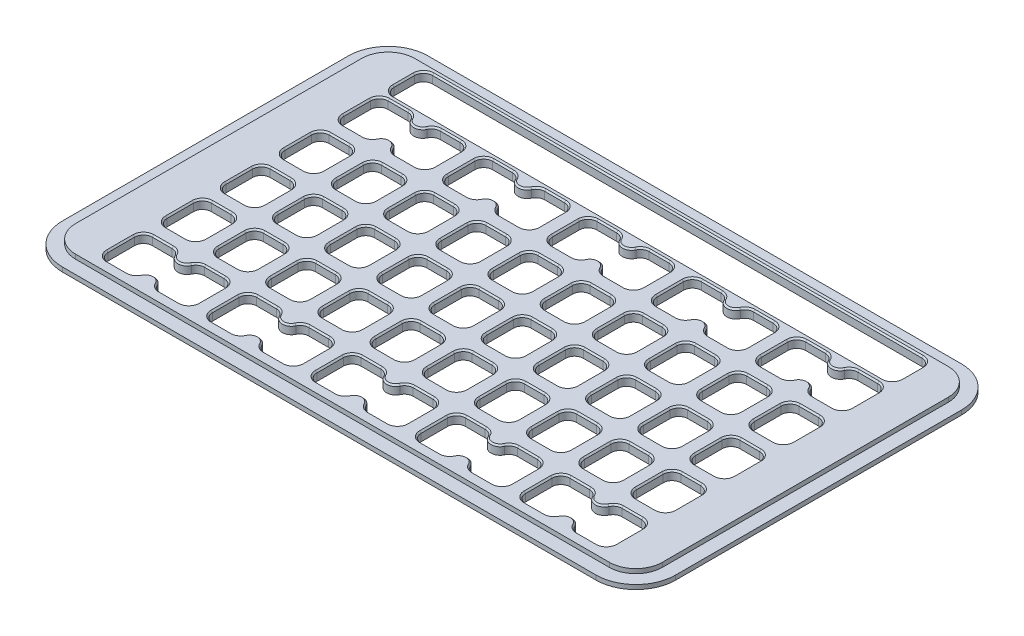
SolidWorks part; units mm, degrees
ref_plane "Front Plane" through (0, 0, 0) normal (0, 0, 1) x (1, 0, 0)
ref_plane "Top Plane" through (0, 0, 0) normal (0, 1, 0) x (1, 0, 0)
ref_plane "Right Plane" through (0, 0, 0) normal (1, 0, 0) x (0, 0, -1)
sketch "Sketch1" plane through (0, 0, 0) normal (0, 1, 0) x (1, 0, 0)
  line L1 (-104, -62) -> (104, -62)
  line L2 (-104, -62) -> (-104, 62)
  line L3 (-104, 62) -> (104, 62)
  line L4 (104, -62) -> (104, 62)
  line L5 (-104, -62) -> (104, 62) construction
  line L6 (-104, 62) -> (104, -62) construction
  point P0 (0, 0)
  dimension "D1" = 208
  dimension "D2" = 124
extrude "Outer Profile" add sketch "Sketch1" along normal blind 1.5
sketch "Sketch2" plane through (0, 1.5, 0) normal (0, 1, 0) x (1, 0, 0)
  line L1 (-99.5, -57.5) -> (99.5, -57.5)
  line L2 (-99.5, -57.5) -> (-99.5, 57.5)
  line L3 (-99.5, 57.5) -> (99.5, 57.5)
  line L4 (99.5, -57.5) -> (99.5, 57.5)
  line L5 (-99.5, -57.5) -> (99.5, 57.5) construction
  line L6 (-99.5, 57.5) -> (99.5, -57.5) construction
  point P0 (0, 0)
  dimension "D1" = 199
  dimension "D2" = 115
extrude "Inner Profile" add sketch "Sketch2" along normal blind 1.5
fillet "Fillet1" radius 9 4 edges at (99.5, 2.25, 57.5) (99.5, 2.25, -57.5) (-99.5, 2.25, -57.5) (-99.5, 2.25, 57.5)
fillet "Fillet2" radius 13.5 4 edges at (-104, 0.75, -62) (104, 0.75, -62) (104, 0.75, 62) (-104, 0.75, 62)
sketch "Sketch3" plane through (0, 3, 0) normal (0, 1, 0) x (1, 0, 0)
  line L1 (-86, -54) -> (86, -54) construction
  line L2 (-86, -54) -> (-86, 54) construction
  line L3 (-86, 54) -> (86, 54) construction
  line L4 (86, -54) -> (86, 54) construction
  line L5 (-86, -54) -> (86, 54) construction
  line L6 (-86, 54) -> (86, -54) construction
  point P0 (0, 0)
  dimension "D1" = 172
  dimension "D2" = 108
sketch "Sketch4" plane through (0, 3, 0) normal (0, 1, 0) x (1, 0, 0)
  line L0 (-86, -54) -> (-86, 54) construction
  line L1 (-86, 43) -> (86, 43)
  line L2 (-86, 43) -> (-86, 56)
  line L3 (-86, 56) -> (86, 56)
  line L4 (86, 43) -> (86, 56)
  line L10 (-86, 54) -> (86, 54) construction
  dimension "D1" = 2
  dimension "D2" = 11
  dimension "D3" = 172
extrude "Message Bar" cut sketch "Sketch4" against normal through all
sketch "Sketch5" plane through (0, 3, 0) normal (0, 1, 0) x (1, 0, 0)
  line L0 (-86, -54) -> (86, -54) construction
  line L1 (-12.2, -54) -> (-5.5, -54)
  line L2 (-15.2, -51) -> (-15.2, -42)
  line L3 (-12.2, -39) -> (-5.5, -39)
  line L4 (-2.5, -51) -> (-2.5, -42)
  line L5 (-8.85, -39) -> (-8.85, -54) construction
  line L6 (0, 0) -> (0, -37.3494) construction
  line L7 (-86, -54) -> (86, 54) construction
  arc A0 (-5.5, -54) -> (-2.5, -51) centre (-5.5, -51) ccw
  arc A1 (-12.2, -54) -> (-15.2, -51) centre (-12.2, -51) cw
  arc A2 (-5.5, -39) -> (-2.5, -42) centre (-5.5, -42) cw
  arc A3 (-15.2, -42) -> (-12.2, -39) centre (-12.2, -42) cw
  point P15 (-2.5, -54)
  point P18 (-15.2, -54)
  point P23 (-15.2, -39)
  dimension "D4" = 3
  dimension "D1" = 12.7
  dimension "D2" = 15
  dimension "D3" = 8.85
extrude "Cutout" cut sketch "Sketch5" against normal through all
pattern_linear "Cutouts" count 5 spacing 17.7 along (-1, 0, 0) count 5 spacing 20 along (0, 0, -1) of "Cutout"
mirror "Mirror Cutouts" about plane through (0, 0, 0) normal (1, 0, 0) of "Cutouts", "Cutout"
fillet "Corner Rad" radius 3 4 edges at (86, 1.5, -43) (86, 1.5, -56) (-86, 1.5, -43) (-86, 1.5, -56)
sketch "Sketch6" plane through (0, 3, 0) normal (0, 1, 0) x (1, 0, 0)
  line L1 (-70.8, 40.5714) -> (-70.8, 26.4286) construction
  line L2 (-70.8, 33.5) -> (-73.3, 33.5) construction
  line L3 (-73.3, 29) -> (-73.3, 38) construction
  line L4 (-68.3, 38) -> (-68.3, 29) construction
  line L5 (-68.3, 38) -> (-68.3, 29)
  line L6 (-73.3, 29) -> (-73.3, 38)
  arc A0 (-73.5824, 39.2706) -> (-68.0176, 39.2706) centre (-70.8, 40.5714) ccw
  arc A1 (-73.3, 38) -> (-76.3, 41) centre (-76.3, 38) ccw construction
  arc A2 (-65.3, 41) -> (-68.3, 38) centre (-65.3, 38) ccw construction
  arc A3 (-73.5824, 27.7294) -> (-68.0176, 27.7294) centre (-70.8, 26.4286) cw
  arc A4 (-76.3, 26) -> (-73.3, 29) centre (-76.3, 29) ccw construction
  arc A5 (-68.3, 29) -> (-65.3, 26) centre (-65.3, 29) ccw construction
  arc A6 (-73.3, 38) -> (-73.5824, 39.2706) centre (-76.3, 38) ccw
  arc A7 (-68.0176, 39.2706) -> (-68.3, 38) centre (-65.3, 38) ccw
  arc A8 (-73.5824, 27.7294) -> (-73.3, 29) centre (-76.3, 29) ccw
  arc A9 (-68.3, 29) -> (-68.0176, 27.7294) centre (-65.3, 29) ccw
  dimension "D1" = 8
extrude "Opening" cut sketch "Sketch6" against normal through all
pattern_linear "Openings" count 5 spacing 35.4 along (1, 0, 0) count 2 spacing 80 along (0, 0, 1) of "Opening"
chamfer "Chamfer" distance 0.5 angle 45 408 edges at (38.7787, 3, 33.1213) (37.9, 3, 26.5) (38.7787, 3, 19.8787) (44.25, 3, 19) (49.7213, 3, 19.8787) (50.6, 3, 26.5) (49.7213, 3, 33.1213) (44.25, 3, 34) (38.7787, 3, 13.1213) (37.9, 3, 6.5) (38.7787, 3, -0.1213) (44.25, 3, -1) (49.7213, 3, -0.1213) (50.6, 3, 6.5) (49.7213, 3, 13.1213) (44.25, 3, 14) (-3.8894, 3, 53.531) (38.7787, 3, -6.8787) (37.9, 3, -13.5) (38.7787, 3, -20.1213) (44.25, 3, -21) (49.7213, 3, -20.1213) (50.6, 3, -13.5) (49.7213, 3, -6.8787) (44.25, 3, -6) (-8.85, 3, 39) (-14.3213, 3, 39.8787) (-15.2, 3, 46.5) (-14.3213, 3, 53.1213) (-8.85, 3, 54) (39.2894, 3, -26.469) (44.25, 3, -41) (49.7213, 3, -40.1213) (50.6, 3, -33.5) (49.7213, 3, -26.8787) (44.25, 3, -26) (56.4787, 3, 53.1213) (55.6, 3, 46.5) (56.4787, 3, 39.8787) (61.95, 3, 39) (66.9106, 3, 39.469) (61.95, 3, 54) (56.4787, 3, 33.1213) (55.6, 3, 26.5) (56.4787, 3, 19.8787) (61.95, 3, 19) (67.4213, 3, 19.8787) (68.3, 3, 26.5) (67.4213, 3, 33.1213) (61.95, 3, 34) (56.4787, 3, 13.1213) (55.6, 3, 6.5) (56.4787, 3, -0.1213) (61.95, 3, -1) (67.4213, 3, -0.1213) (68.3, 3, 6.5) (67.4213, 3, 13.1213) (61.95, 3, 14) (56.4787, 3, -6.8787) (55.6, 3, -13.5) (56.4787, 3, -20.1213) (61.95, 3, -21) (67.4213, 3, -20.1213) (68.3, 3, -13.5) (67.4213, 3, -6.8787) (61.95, 3, -6) (56.4787, 3, -26.8787) (55.6, 3, -33.5) (56.4787, 3, -40.1213) (61.95, 3, -41) (66.9106, 3, -40.531) (61.95, 3, -26) (74.6894, 3, 53.531) (79.65, 3, 39) (85.1213, 3, 39.8787) (86, 3, 46.5) (85.1213, 3, 53.1213) (79.65, 3, 54) (74.1787, 3, 33.1213) (73.3, 3, 26.5) (74.1787, 3, 19.8787) (79.65, 3, 19) (85.1213, 3, 19.8787) (86, 3, 26.5) (85.1213, 3, 33.1213) (79.65, 3, 34) (74.1787, 3, 13.1213) (73.3, 3, 6.5) (74.1787, 3, -0.1213) (79.65, 3, -1) (85.1213, 3, -0.1213) (86, 3, 6.5) (85.1213, 3, 13.1213) (79.65, 3, 14) (74.1787, 3, -6.8787) (73.3, 3, -13.5) (74.1787, 3, -20.1213) (79.65, 3, -21) (85.1213, 3, -20.1213) (86, 3, -13.5) (85.1213, 3, -6.8787) (79.65, 3, -6) (74.6894, 3, -26.469) (79.65, 3, -41) (85.1213, 3, -40.1213) (86, 3, -33.5) (85.1213, 3, -26.8787) (79.65, 3, -26) (-3.3787, 3, 33.1213) (-2.5, 3, 26.5) (-3.3787, 3, 19.8787) (-8.85, 3, 19) (-14.3213, 3, 19.8787) (-15.2, 3, 26.5) (-14.3213, 3, 33.1213) (-8.85, 3, 34) (86, 3, -49.5) (0, 3, -43) (0, 3, -56) (-86, 3, -49.5) (85.1213, 3, -43.8787) (85.1213, 3, -55.1213) (-85.1213, 3, -43.8787) (-85.1213, 3, -55.1213) (-74.6894, 3, -40.531) (-66.9106, 3, -26.469) (-70.8, 3, -29.5) (-70.8, 3, -37.5) (-74.6894, 3, 39.469) (-66.9106, 3, 53.531) (-70.8, 3, 50.5) (-70.8, 3, 42.5) (-39.2894, 3, -40.531) (-31.5106, 3, -26.469) (-35.4, 3, -29.5) (-35.4, 3, -37.5) (-39.2894, 3, 39.469) (-31.5106, 3, 53.531) (-35.4, 3, 50.5) (-35.4, 3, 42.5) (3.8894, 3, -40.531) (-3.8894, 3, -40.531) (0, 3, -29.5) (0, 3, -37.5) (3.8894, 3, 39.469) (-3.8894, 3, 39.469) (0, 3, 50.5) (0, 3, 42.5) (39.2894, 3, -40.531) (31.5106, 3, -26.469) (35.4, 3, -29.5) (35.4, 3, -37.5) (39.2894, 3, 39.469) (-3.3787, 3, 13.1213) (31.5106, 3, 53.531) (-2.5, 3, 6.5) (-3.3787, 3, -0.1213) (35.4, 3, 50.5) (-8.85, 3, -1) (35.4, 3, 42.5) (-14.3213, 3, -0.1213) (-15.2, 3, 6.5) (-14.3213, 3, 13.1213) (-8.85, 3, 14) (74.6894, 3, -40.531) (66.9106, 3, -26.469) (70.8, 3, -29.5) (70.8, 3, -37.5) (74.6894, 3, 39.469) (66.9106, 3, 53.531) (70.8, 3, 50.5) (70.8, 3, 42.5) (-3.3787, 3, -6.8787) (-2.5, 3, -13.5) (-3.3787, 3, -20.1213) (-8.85, 3, -21) (-14.3213, 3, -20.1213) (-15.2, 3, -13.5) (-14.3213, 3, -6.8787) (-8.85, 3, -6) (-3.8894, 3, -26.469) (-8.85, 3, -41) (-14.3213, 3, -40.1213) (-15.2, 3, -33.5) (-14.3213, 3, -26.8787) (-8.85, 3, -26) (-21.0787, 3, 53.1213) (-20.2, 3, 46.5) (-21.0787, 3, 39.8787) (-26.55, 3, 39) (-31.5106, 3, 39.469) (-26.55, 3, 54) (-21.0787, 3, 33.1213) (-20.2, 3, 26.5) (-21.0787, 3, 19.8787) (-26.55, 3, 19) (-32.0213, 3, 19.8787) (-32.9, 3, 26.5) (-32.0213, 3, 33.1213) (-26.55, 3, 34) (-21.0787, 3, 13.1213) (-20.2, 3, 6.5) (-21.0787, 3, -0.1213) (-26.55, 3, -1) (-32.0213, 3, -0.1213) (-32.9, 3, 6.5) (-32.0213, 3, 13.1213) (-26.55, 3, 14) (-21.0787, 3, -6.8787) (-20.2, 3, -13.5) (-21.0787, 3, -20.1213) (-26.55, 3, -21) (-32.0213, 3, -20.1213) (-32.9, 3, -13.5) (-32.0213, 3, -6.8787) (-26.55, 3, -6) (-21.0787, 3, -26.8787) (-20.2, 3, -33.5) (-21.0787, 3, -40.1213) (-26.55, 3, -41) (-31.5106, 3, -40.531) (-26.55, 3, -26) (-39.2894, 3, 53.531) (-44.25, 3, 39) (-49.7213, 3, 39.8787) (-50.6, 3, 46.5) (-49.7213, 3, 53.1213) (-44.25, 3, 54) (-38.7787, 3, 33.1213) (-37.9, 3, 26.5) (-38.7787, 3, 19.8787) (-44.25, 3, 19) (-49.7213, 3, 19.8787) (-50.6, 3, 26.5) (-49.7213, 3, 33.1213) (-44.25, 3, 34) (-38.7787, 3, 13.1213) (-37.9, 3, 6.5) (-38.7787, 3, -0.1213) (-44.25, 3, -1) (-49.7213, 3, -0.1213) (-50.6, 3, 6.5) (-49.7213, 3, 13.1213) (-44.25, 3, 14) (-38.7787, 3, -6.8787) (-37.9, 3, -13.5) (-38.7787, 3, -20.1213) (-44.25, 3, -21) (-49.7213, 3, -20.1213) (-50.6, 3, -13.5) (-49.7213, 3, -6.8787) (-44.25, 3, -6) (-39.2894, 3, -26.469) (-44.25, 3, -41) (-49.7213, 3, -40.1213) (-50.6, 3, -33.5) (-49.7213, 3, -26.8787) (-44.25, 3, -26) (-56.4787, 3, 53.1213) (-55.6, 3, 46.5) (-56.4787, 3, 39.8787) (-61.95, 3, 39) (-66.9106, 3, 39.469) (-61.95, 3, 54) (-56.4787, 3, 33.1213) (-55.6, 3, 26.5) (-56.4787, 3, 19.8787) (-61.95, 3, 19) (-67.4213, 3, 19.8787) (-68.3, 3, 26.5) (-67.4213, 3, 33.1213) (-61.95, 3, 34) (-56.4787, 3, 13.1213) (-55.6, 3, 6.5) (-56.4787, 3, -0.1213) (-61.95, 3, -1) (-67.4213, 3, -0.1213) (-68.3, 3, 6.5) (-67.4213, 3, 13.1213) (-61.95, 3, 14) (-56.4787, 3, -6.8787) (-55.6, 3, -13.5) (-56.4787, 3, -20.1213) (-61.95, 3, -21) (-67.4213, 3, -20.1213) (-68.3, 3, -13.5) (-67.4213, 3, -6.8787) (-61.95, 3, -6) (-56.4787, 3, -26.8787) (-55.6, 3, -33.5) (-56.4787, 3, -40.1213) (-61.95, 3, -41) (-66.9106, 3, -40.531) (-61.95, 3, -26) (-74.6894, 3, 53.531) (-79.65, 3, 39) (-85.1213, 3, 39.8787) (-86, 3, 46.5) (-85.1213, 3, 53.1213) (-79.65, 3, 54) (-74.1787, 3, 33.1213) (-73.3, 3, 26.5) (-74.1787, 3, 19.8787) (-79.65, 3, 19) (-85.1213, 3, 19.8787) (-86, 3, 26.5) (-85.1213, 3, 33.1213) (-79.65, 3, 34) (-74.1787, 3, 13.1213) (-73.3, 3, 6.5) (-74.1787, 3, -0.1213) (-79.65, 3, -1) (-85.1213, 3, -0.1213) (-86, 3, 6.5) (-85.1213, 3, 13.1213) (-79.65, 3, 14) (-74.1787, 3, -6.8787) (-73.3, 3, -13.5) (-74.1787, 3, -20.1213) (-79.65, 3, -21) (-85.1213, 3, -20.1213) (-86, 3, -13.5) (-85.1213, 3, -6.8787) (-79.65, 3, -6) (-74.6894, 3, -26.469) (-79.65, 3, -41) (-85.1213, 3, -40.1213) (-86, 3, -33.5) (-85.1213, 3, -26.8787) (-79.65, 3, -26) (3.8894, 3, 53.531) (8.85, 3, 39) (14.3213, 3, 39.8787) (15.2, 3, 46.5) (14.3213, 3, 53.1213) (8.85, 3, 54) (3.3787, 3, 33.1213) (2.5, 3, 26.5) (3.3787, 3, 19.8787) (8.85, 3, 19) (14.3213, 3, 19.8787) (15.2, 3, 26.5) (14.3213, 3, 33.1213) (8.85, 3, 34) (3.3787, 3, 13.1213) (2.5, 3, 6.5) (3.3787, 3, -0.1213) (8.85, 3, -1) (14.3213, 3, -0.1213) (15.2, 3, 6.5) (14.3213, 3, 13.1213) (8.85, 3, 14) (3.3787, 3, -6.8787) (2.5, 3, -13.5) (3.3787, 3, -20.1213) (8.85, 3, -21) (14.3213, 3, -20.1213) (15.2, 3, -13.5) (14.3213, 3, -6.8787) (8.85, 3, -6) (3.8894, 3, -26.469) (8.85, 3, -41) (14.3213, 3, -40.1213) (15.2, 3, -33.5) (14.3213, 3, -26.8787) (8.85, 3, -26) (21.0787, 3, 53.1213) (20.2, 3, 46.5) (21.0787, 3, 39.8787) (26.55, 3, 39) (31.5106, 3, 39.469) (26.55, 3, 54) (21.0787, 3, 33.1213) (20.2, 3, 26.5) (21.0787, 3, 19.8787) (26.55, 3, 19) (32.0213, 3, 19.8787) (32.9, 3, 26.5) (32.0213, 3, 33.1213) (26.55, 3, 34) (21.0787, 3, 13.1213) (20.2, 3, 6.5) (21.0787, 3, -0.1213) (26.55, 3, -1) (32.0213, 3, -0.1213) (32.9, 3, 6.5) (32.0213, 3, 13.1213) (26.55, 3, 14) (21.0787, 3, -6.8787) (20.2, 3, -13.5) (21.0787, 3, -20.1213) (26.55, 3, -21) (32.0213, 3, -20.1213) (32.9, 3, -13.5) (32.0213, 3, -6.8787) (26.55, 3, -6) (21.0787, 3, -26.8787) (20.2, 3, -33.5) (21.0787, 3, -40.1213) (26.55, 3, -41) (31.5106, 3, -40.531) (26.55, 3, -26) (39.2894, 3, 53.531) (44.25, 3, 39) (49.7213, 3, 39.8787) (50.6, 3, 46.5) (49.7213, 3, 53.1213) (44.25, 3, 54)
